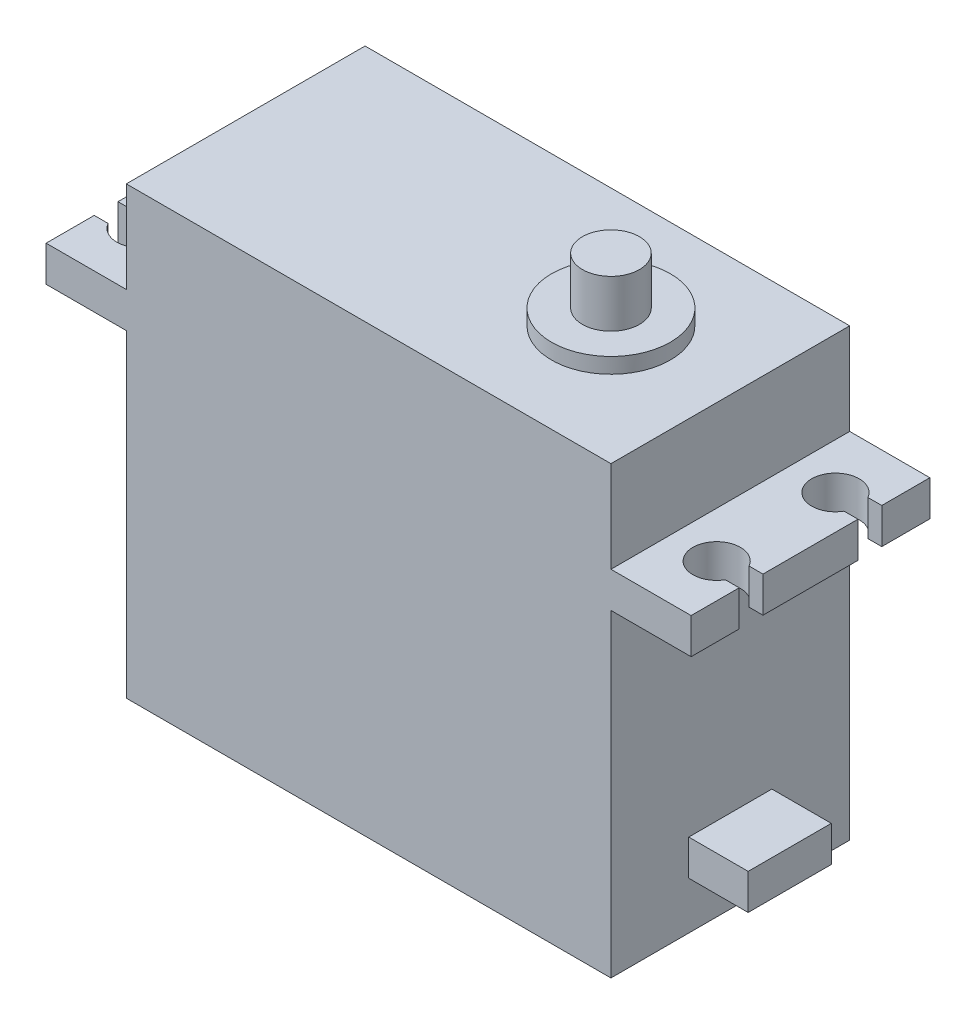
SolidWorks part; units mm, degrees
ref_plane "Front Plane" through (0, 0, 0) normal (0, 0, 1) x (1, 0, 0)
ref_plane "Top Plane" through (0, 0, 0) normal (0, 1, 0) x (1, 0, 0)
ref_plane "Right Plane" through (0, 0, 0) normal (1, 0, 0) x (0, 0, -1)
sketch "Sketch2" plane through (0, 0, 0) normal (0, 1, 0) x (1, 0, 0)
  line L0 (0, 0) -> (0, 10.05) construction
  line L1 (0, 0) -> (10.05, 0) construction
  line L2 (0, 0) -> (0, -10.05) construction
  line L3 (0, 0) -> (-30.75, 0) construction
  line L4 (-34.6, 5) -> (-34.6, -5) construction
  line L5 (-30.75, 10.05) -> (10.05, 10.05)
  line L6 (-30.75, 10.05) -> (-30.75, -10.05)
  line L7 (-30.75, -10.05) -> (10.05, -10.05)
  line L8 (10.05, 10.05) -> (10.05, -10.05)
  line L9 (-30.75, 10.05) -> (-37.5, 10.05) construction
  line L10 (-37.5, 10.05) -> (-37.5, -10.05) construction
  line L11 (-37.5, -10.05) -> (-30.75, -10.05) construction
  line L12 (-10.35, 10.05) -> (-10.35, -10.05) construction
  line L13 (13.9, 5) -> (13.9, -5) construction
  line L14 (-36.6, 5) -> (-37.5, 5) construction
  line L15 (10.05, 10.05) -> (16.8, 10.05) construction
  line L16 (16.8, 10.05) -> (16.8, -10.05) construction
  line L17 (16.8, -10.05) -> (10.05, -10.05) construction
  line L18 (10.05, 3.5) -> (15.05, 3.5) construction
  line L19 (15.05, 3.5) -> (15.05, -3.5) construction
  line L20 (15.05, -3.5) -> (10.05, -3.5) construction
  circle A0 centre (0, 0) radius 2.4
  circle A1 centre (0, 0) radius 10.05 construction
  circle A2 centre (-34.6, 5) radius 2
  circle A3 centre (-34.6, -5) radius 2
  circle A4 centre (13.9, -5) radius 2
  circle A5 centre (13.9, 5) radius 2
  circle A6 centre (0, 0) radius 5 construction
  dimension "D1" = 4.8
  dimension "D6" = 4
  dimension "D8" = 10
  dimension "D2" = 40.8
  dimension "D3" = 20.1
  dimension "D4" = 10
  dimension "D5" = 48.5
  dimension "D7" = 0.9
  dimension "D9" = 54.3
  dimension "D10" = 7
  dimension "D11" = 5
sketch "Sketch3" plane through (0, 0, 0) normal (0, 0, 1) x (1, 0, 0)
  line L0 (-30.75, 0) -> (-30.75, 26.8)
  line L1 (-30.75, 26.8) -> (-37.5, 26.8)
  line L2 (-37.5, 26.8) -> (-37.5, 29.8)
  line L3 (-37.5, 29.8) -> (-30.75, 29.8)
  line L4 (-30.75, 29.8) -> (-30.75, 37.5)
  line L5 (-30.75, 37.5) -> (10.05, 37.5)
  line L6 (10.05, 37.5) -> (10.05, 29.8)
  line L7 (10.05, 29.8) -> (16.8, 29.8)
  line L8 (16.8, 29.8) -> (16.8, 26.8)
  line L9 (16.8, 26.8) -> (10.05, 26.8)
  line L10 (10.05, 26.8) -> (10.05, 0)
  line L11 (10.05, 0) -> (-30.75, 0)
  line L12 (-10.35, 0) -> (-10.35, 37.5) construction
  line L13 (2.4, 0) -> (2.4, 42.8) construction
  line L14 (2.4, 0) -> (-2.4, 0) construction
  line L15 (2.4, 42.8) -> (-2.4, 42.8) construction
  line L16 (-2.4, 42.8) -> (-2.4, 0) construction
  line L17 (10.05, 0) -> (-10.05, 0) construction
  line L18 (-5, 38.8) -> (5, 38.8) construction
  line L19 (-5, 0) -> (-5, 38.8) construction
  line L20 (5, 38.8) -> (5, 0) construction
  line L21 (10.05, 4) -> (15.05, 4) construction
  line L22 (15.05, 4) -> (15.05, 7) construction
  line L23 (15.05, 7) -> (10.05, 7) construction
  line L24 (5, 38.8) -> (19.8, 38.8) construction
  line L26 (19.8, 38.8) -> (19.8, 26.8) construction
  line L28 (16.8, 26.8) -> (19.8, 26.8) construction
  dimension "D1" = 26.8
  dimension "D2" = 3
  dimension "D3" = 4
  dimension "D4" = 38.8
  dimension "D5" = 1.3
  dimension "D6" = 12
  dimension "D7" = 7
  dimension "D8" = 4
  dimension "D9" = 37.5
extrude "Boss-Extrude1" add sketch "Sketch3" along normal up to vertex (10.05 mm away) from vertex up to point (-30.75, 0, 10.05) starting at point (-30.75, 0, -10.05)
sketch "Sketch4" plane through (0, 29.8, 0) normal (0, 1, 0) x (1, 0, 0)
  line L0 (-10.35, 10.05) -> (-10.35, -10.05) construction
  line L1 (-10.35, 10.05) -> (-10.35, -10.05) construction
  line L2 (-37.5, 10.05) -> (-37.5, -10.05) construction
  line L4 (-37.5, 6) -> (-37.5, 4)
  line L5 (16.8, -6) -> (15.6321, -6)
  line L6 (-10.35, 0) -> (-37.5, 0) construction
  line L7 (-37.5, 4) -> (-36.3321, 4)
  line L8 (-37.5, 6) -> (-36.3321, 6)
  line L9 (-34.6, 5) -> (-37.5, 5) construction
  line L10 (-37.5, -4) -> (-37.5, -6)
  line L11 (-37.5, -4) -> (-36.3321, -4)
  line L12 (-37.5, -6) -> (-36.3321, -6)
  line L13 (16.8, -4) -> (16.8, -6)
  line L14 (16.8, -4) -> (15.6321, -4)
  line L15 (16.8, 4) -> (15.6321, 4)
  line L16 (16.8, 6) -> (16.8, 4)
  line L17 (16.8, 6) -> (15.6321, 6)
  circle A0 centre (-34.6, -5) radius 2 construction
  circle A1 centre (-34.6, 5) radius 2 construction
  circle A2 centre (13.9, 5) radius 2 construction
  circle A3 centre (13.9, -5) radius 2 construction
  arc A4 (-36.3321, -6) -> (-36.3321, -4) centre (-34.6, -5) ccw
  arc A5 (-36.3321, 4) -> (-36.3321, 6) centre (-34.6, 5) ccw
  arc A6 (15.6321, 6) -> (15.6321, 4) centre (13.9, 5) ccw
  arc A7 (15.6321, -4) -> (15.6321, -6) centre (13.9, -5) ccw
  dimension "D1" = 2
extrude "Cut-Extrude1" cut sketch "Sketch4" against normal through all
sketch "Sketch5" plane through (0, 37.5, 0) normal (0, 1, 0) x (1, 0, 0)
  circle A0 centre (0, 0) radius 5 construction
  circle A1 centre (0, 0) radius 5
extrude "Boss-Extrude2" add sketch "Sketch5" along normal up to vertex (1.3 mm away) up to point (-5, 38.8, 0)
sketch "Sketch6" plane through (0, 38.8, 0) normal (0, 1, 0) x (1, 0, 0)
  circle A0 centre (0, 0) radius 2.4 construction
  circle A1 centre (0, 0) radius 2.4
extrude "Boss-Extrude3" add sketch "Sketch6" along normal up to vertex (4 mm away) up to point (-2.4, 42.8, 0)
sketch "Sketch7" plane through (0, 38.8, 0) normal (0, 1, 0) x (1, 0, 0)
  circle A0 centre (0, 0) radius 2.85
  dimension "D1" = 5.7
sketch "Sketch8" plane through (10.05, 0, 0) normal (1, 0, 0) x (0, 0, -1)
  line L1 (-3.5, 7) -> (3.5, 7)
  line L2 (-3.5, 7) -> (-3.5, 4)
  line L3 (-3.5, 4) -> (3.5, 4)
  line L4 (3.5, 7) -> (3.5, 4)
extrude "Boss-Extrude4" add sketch "Sketch8" along normal up to vertex (5 mm away) up to point (15.05, 7, 0)
